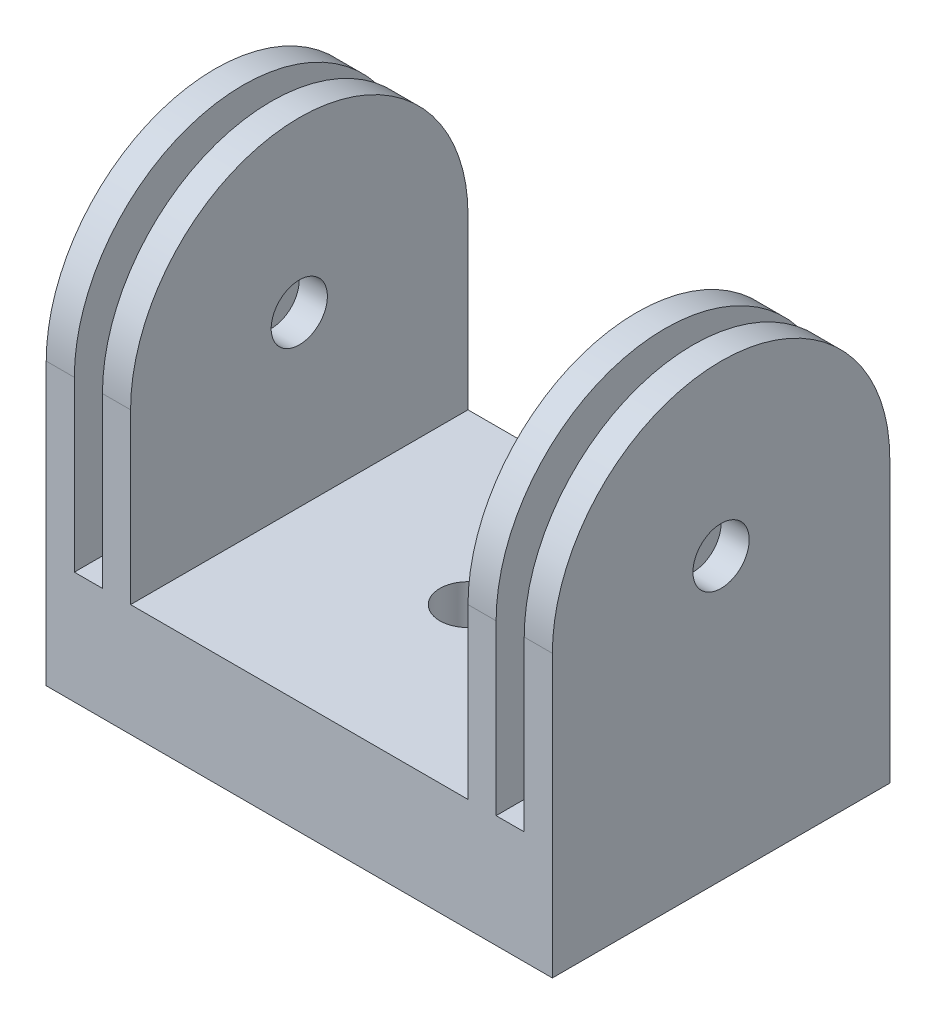
SolidWorks part; units mm, degrees
ref_plane "Front Plane" through (0, 0, 0) normal (0, 0, 1) x (1, 0, 0)
ref_plane "Top Plane" through (0, 0, 0) normal (0, 1, 0) x (1, 0, 0)
ref_plane "Right Plane" through (0, 0, 0) normal (1, 0, 0) x (0, 0, -1)
sketch "Sketch1" plane through (0, 0, 0) normal (0, 1, 0) x (1, 0, 0)
  line L1 (-22.5, 15) -> (22.5, 15)
  line L2 (-22.5, 15) -> (-22.5, -15)
  line L3 (-22.5, -15) -> (22.5, -15)
  line L4 (22.5, 15) -> (22.5, -15)
  line L5 (0, -15) -> (0, 15) construction
  line L6 (-22.5, 0) -> (22.5, 0) construction
  circle A0 centre (0, 0) radius 2.5
  point P0 (0, 0)
  dimension "D1" = 45
  dimension "D3" = 5
  dimension "D2" = 30
extrude "Boss-Extrude1" add sketch "Sketch1" along normal blind 10 contours L4 L1 L2 L3 A0
sketch "Sketch2" plane through (22.5, 0, 0) normal (1, 0, 0) x (0, 0, -1)
  line L0 (15, 10) -> (15, 0) construction
  line L1 (-15, 10) -> (15, 10)
  line L2 (-15, 10) -> (-15, 25)
  line L4 (15, 10) -> (15, 25)
  arc A0 (-15, 25) -> (15, 25) centre (0, 25) cw
  circle A1 centre (0, 25) radius 2.5
  point P9 (0, 0)
  dimension "D2" = 5
  dimension "D4" = 15
  dimension "D1" = 15
  dimension "D3" = 10
extrude "Boss-Extrude2" add sketch "Sketch2" against normal blind 2.5
ref_plane "Plane1" through (18.75, 0, 0) normal (1, 0, 0) x (0, 0, -1)
mirror "Mirror2" about plane through (18.75, 0, 0) normal (1, 0, 0) of "Boss-Extrude2"
mirror "Mirror3" about plane through (0, 0, 0) normal (1, 0, 0) of "Mirror2"
